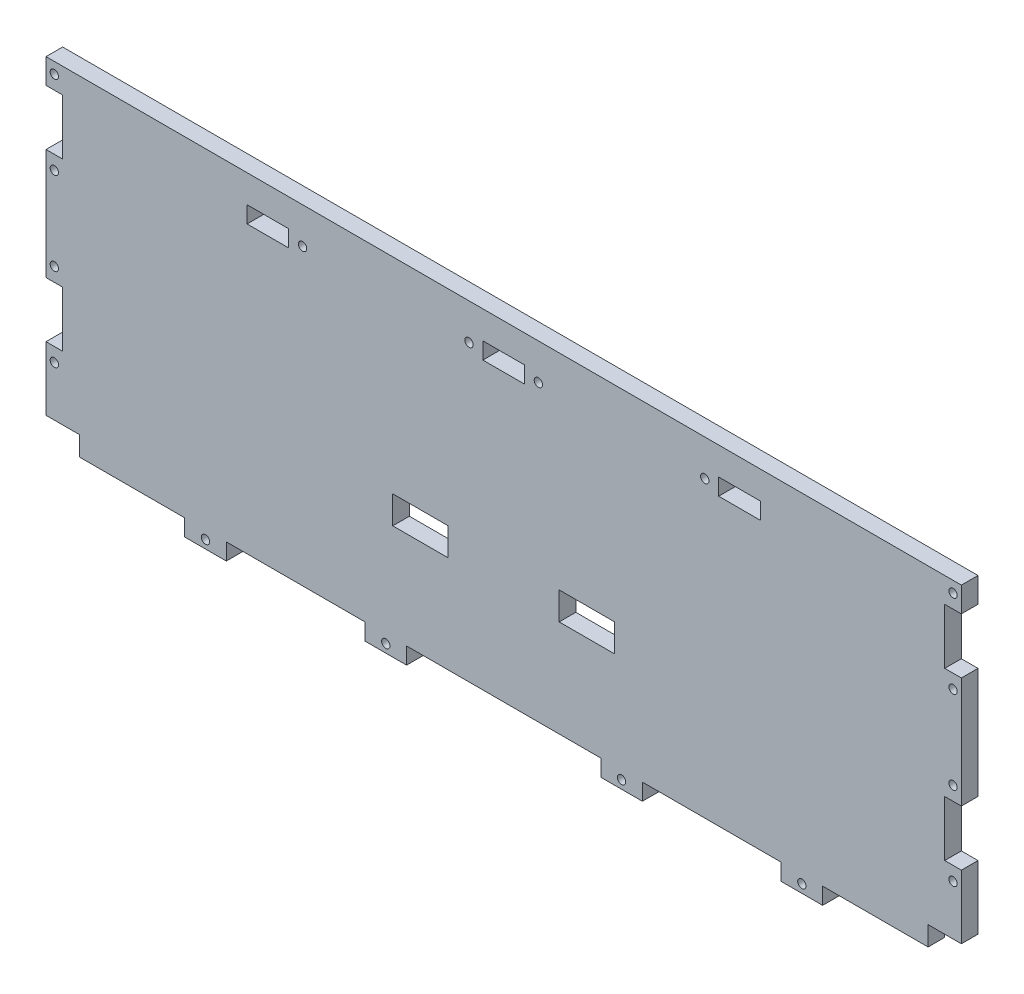
SolidWorks part; units mm, degrees
ref_plane "Plan de face" through (0, 0, 0) normal (0, 0, 1) x (1, 0, 0)
ref_plane "Plan de dessus" through (0, 0, 0) normal (0, 1, 0) x (1, 0, 0)
ref_plane "Plan de droite" through (0, 0, 0) normal (1, 0, 0) x (0, 0, -1)
sketch "Esquisse1" plane through (0, 0, 0) normal (0, 0, 1) x (1, 0, 0)
  line L0 (97.3951, 0) -> (-118.5049, 0) construction
  line L1 (-165, 119) -> (165, 119)
  line L2 (-165, 119) -> (-165, -119)
  line L3 (-165, -119) -> (165, -119)
  line L4 (165, 119) -> (165, -119)
  line L5 (0, 79.3588) -> (0, -79.3588) construction
  line L6 (-92.5, -10) -> (-77.5, -10)
  line L7 (-92.5, -10) -> (-92.5, -16)
  line L8 (-92.5, -16) -> (-77.5, -16)
  line L9 (-77.5, -10) -> (-77.5, -16)
  line L10 (-7.5, -10) -> (7.5, -10)
  line L11 (-7.5, -10) -> (-7.5, -16)
  line L12 (-7.5, -16) -> (7.5, -16)
  line L13 (7.5, -10) -> (7.5, -16)
  line L14 (77.5, -10) -> (92.5, -10)
  line L15 (77.5, -10) -> (77.5, -16)
  line L16 (77.5, -16) -> (92.5, -16)
  line L17 (92.5, -10) -> (92.5, -16)
  line L18 (20, -74) -> (20, -84)
  line L19 (-40, -74) -> (-20, -74)
  line L20 (-40, -74) -> (-40, -84)
  line L21 (-40, -84) -> (-20, -84)
  line L22 (-20, -74) -> (-20, -84)
  line L23 (40, -84) -> (20, -84)
  line L24 (40, -74) -> (40, -84)
  line L25 (40, -74) -> (20, -74)
  dimension "D1" = 238
  dimension "D2" = 330
  dimension "D3" = 165
  dimension "D4" = 119
  dimension "D5" = 15
  dimension "D6" = 6
  dimension "D7" = 6
  dimension "D8" = 15
  dimension "D9" = 6
  dimension "D10" = 15
  dimension "D11" = 70
  dimension "D12" = 70
  dimension "D13" = 103
  dimension "D14" = 72.5
  dimension "D15" = 10
  dimension "D16" = 20
  dimension "D17" = 35
  dimension "D18" = 40
extrude "Boss.-Extru.1" add sketch "Esquisse1" along normal blind 6
sketch "Esquisse2" plane through (0, 0, 6) normal (0, 0, 1) x (1, 0, 0)
  line L0 (243.146, 0) -> (-260.0003, 0) construction
  line L1 (0, 180.4713) -> (0, -129.6072) construction
  line L3 (-165, -119) -> (165, -119) construction
  line L4 (-115, -119) -> (-100, -119)
  line L5 (-115, -119) -> (-115, -125)
  line L6 (-115, -125) -> (-100, -125)
  line L8 (-100, -119) -> (-100, -125)
  line L9 (-165, 119) -> (-165, -119) construction
  line L10 (-50, -119) -> (-35, -119)
  line L11 (-50, -119) -> (-50, -125)
  line L12 (-50, -125) -> (-35, -125)
  line L13 (-35, -119) -> (-35, -125)
  line L14 (35, -119) -> (35, -125)
  line L15 (50, -125) -> (35, -125)
  line L16 (50, -119) -> (50, -125)
  line L17 (50, -119) -> (35, -119)
  line L18 (100, -119) -> (100, -125)
  line L19 (115, -125) -> (100, -125)
  line L20 (115, -119) -> (115, -125)
  line L21 (115, -119) -> (100, -119)
  line M9 (-165, -119) -> (165, -119)
  line M11 (165, 119) -> (-165, 119)
  dimension "D1" = 15
  dimension "D2" = 15
  dimension "D3" = 6
  dimension "D4" = 6
  dimension "D5" = 50
  dimension "D6" = 50
extrude "Boss.-Extru.2" add sketch "Esquisse2" against normal blind 6 contours M11 | M11 | M11 | M11 | M9 | M9 | M9 | M9 region at (107.5, -122, 6) region at (42.5, -122, 6) region at (-42.5, -122, 6) region at (-107.5, -122, 6)
sketch "Esquisse3" plane through (0, 0, 6) normal (0, 0, 1) x (1, 0, 0)
  line L0 (-165, 119) -> (-165, -119) construction
  line L1 (-165, 69) -> (-159, 69)
  line L2 (-165, 69) -> (-165, 89)
  line L3 (-165, 89) -> (-159, 89)
  line L4 (-159, 69) -> (-159, 89)
  line L5 (234.1368, 0) -> (-337.9213, 0) construction
  line L6 (-165, 29) -> (-159, 29)
  line L7 (-165, 29) -> (-165, 9)
  line L8 (-165, 9) -> (-159, 9)
  line L9 (-159, 29) -> (-159, 9)
  line L10 (0, 279.7488) -> (0, -188.1201) construction
  line L11 (165, 119) -> (-165, 119) construction
  line L12 (-159, -29) -> (-159, -9)
  line L13 (-165, -9) -> (-159, -9)
  line L14 (-165, -29) -> (-165, -9)
  line L15 (-165, -29) -> (-159, -29)
  line L16 (-159, -69) -> (-159, -89)
  line L17 (-165, -89) -> (-159, -89)
  line L18 (-165, -69) -> (-165, -89)
  line L19 (-165, -69) -> (-159, -69)
  line L20 (165, -69) -> (159, -69)
  line L21 (165, -69) -> (165, -89)
  line L22 (165, -89) -> (159, -89)
  line L23 (159, -69) -> (159, -89)
  line L24 (165, -29) -> (159, -29)
  line L25 (165, -29) -> (165, -9)
  line L26 (165, -9) -> (159, -9)
  line L27 (159, -29) -> (159, -9)
  line L28 (159, 29) -> (159, 9)
  line L29 (165, 9) -> (159, 9)
  line L30 (165, 29) -> (165, 9)
  line L31 (165, 29) -> (159, 29)
  line L32 (159, 69) -> (159, 89)
  line L33 (165, 89) -> (159, 89)
  line L34 (165, 69) -> (165, 89)
  line L35 (165, 69) -> (159, 69)
  line L36 (153, -119) -> (153, -112)
  line L37 (-165, -119) -> (-153, -119)
  line L38 (-165, -119) -> (-165, -112)
  line L39 (-165, -112) -> (-153, -112)
  line L40 (-153, -119) -> (-153, -112)
  line L41 (165, -112) -> (153, -112)
  line L42 (165, -119) -> (165, -112)
  line L43 (165, -119) -> (153, -119)
  dimension "D1" = 40
  dimension "D2" = 6
  dimension "D3" = 6
  dimension "D4" = 20
  dimension "D5" = 20
  dimension "D6" = 30
  dimension "D7" = 12
  dimension "D8" = 7
extrude "Enlèv. mat.-Extru.1" cut sketch "Esquisse3" against normal blind 6
sketch "Esquisse4" plane through (0, 0, 6) normal (0, 0, 1) x (1, 0, 0)
  line L0 (-162, 121.7279) -> (-162, -131.0602) construction
  line L1 (0, 158.5579) -> (0, -182.4489) construction
  line L2 (165, 119) -> (-165, 119) construction
  line L3 (-106.4439, -13) -> (117.3944, -13) construction
  line L4 (-159, 89) -> (-165, 89) construction
  line L5 (-165, 119) -> (-165, 89) construction
  line L6 (-165, 69) -> (-159, 69) construction
  line L7 (-159, 29) -> (-165, 29) construction
  line L8 (-165, 9) -> (-159, 9) construction
  line L9 (-159, -9) -> (-165, -9) construction
  line L10 (-115, -125) -> (-100, -125) construction
  line L11 (-77.5, -16) -> (-77.5, -10) construction
  line L12 (-165, -29) -> (-159, -29) construction
  line L13 (-159, -69) -> (-165, -69) construction
  line L14 (-165, -89) -> (-159, -89) construction
  line L15 (-7.5, -10) -> (-7.5, -16) construction
  line L16 (162, 121.7279) -> (162, -131.0602) construction
  line L17 (-127.292, -122) -> (137.4892, -122) construction
  line L18 (-77.5, -10) -> (-92.5, -10) construction
  line L21 (-115, -119) -> (-115, -125) construction
  line L22 (-50, -119) -> (-50, -125) construction
  circle A0 centre (-162, 114) radius 1.5
  circle A1 centre (-162, 94) radius 1.5
  circle A2 centre (-162, 64) radius 1.5
  circle A3 centre (-162, 34) radius 1.5
  circle A4 centre (-162, 4) radius 1.5
  circle A5 centre (-107.5, -122) radius 1.5
  circle A6 centre (-162, -4) radius 1.5
  circle A7 centre (-162, -34) radius 1.5
  circle A8 centre (-162, -64) radius 1.5
  circle A9 centre (-162, -94) radius 1.5
  circle A10 centre (-42.5, -122) radius 1.5
  circle A11 centre (-72.5, -13) radius 1.5
  circle A12 centre (162, -94) radius 1.5
  circle A13 centre (162, -64) radius 1.5
  circle A14 centre (162, -34) radius 1.5
  circle A15 centre (162, -4) radius 1.5
  circle A16 centre (42.5, -122) radius 1.5
  circle A17 centre (162, 4) radius 1.5
  circle A18 centre (162, 34) radius 1.5
  circle A19 centre (162, 64) radius 1.5
  circle A20 centre (162, 94) radius 1.5
  circle A21 centre (162, 114) radius 1.5
  circle A22 centre (-12.5, -13) radius 1.5
  circle A23 centre (12.5, -13) radius 1.5
  circle A24 centre (72.5, -13) radius 1.5
  circle A25 centre (107.5, -122) radius 1.5
  dimension "D1" = 3
  dimension "D2" = 3
  dimension "D3" = 3
  dimension "D4" = 3
  dimension "D5" = 3
  dimension "D6" = 3
  dimension "D7" = 3
  dimension "D8" = 3
  dimension "D9" = 3
  dimension "D10" = 3
  dimension "D11" = 3
  dimension "D12" = 5
  dimension "D13" = 5
  dimension "D15" = 5
  dimension "D16" = 5
  dimension "D17" = 5
  dimension "D19" = 3
  dimension "D20" = 5
  dimension "D21" = 5
  dimension "D23" = 3
  dimension "D24" = 3
  dimension "D25" = 7.5
  dimension "D26" = 5
  dimension "D27" = 5
  dimension "D28" = 7.5
  dimension "D14" = 3
  dimension "D18" = 5
  dimension "D22" = 5
  dimension "D29" = 3
extrude "Enlèv. mat.-Extru.2" cut sketch "Esquisse4" against normal blind 6
sketch "Esquisse5" plane through (0, 0, 6) normal (0, 0, 1) x (1, 0, 0)
  line L1 (-174.9982, 0) -> (181.1877, 0)
  line L2 (-174.9982, 0) -> (-174.9982, 137.1433)
  line L3 (-174.9982, 137.1433) -> (181.1877, 137.1433)
  line L4 (181.1877, 0) -> (181.1877, 137.1433)
extrude "Enlèv. mat.-Extru.3" cut sketch "Esquisse5" against normal blind 6
sketch "Esquisse6" plane through (0, 0, 6) normal (0, 0, 1) x (1, 0, 0)
  line L0 (-103.8163, -14.4996) -> (134.12, -14.4996) construction
  arc A0 (-103.2691, -14.4996) -> (-23.2691, -14.4996) centre (-63.2691, -14.4996) cw construction
  arc A1 (31.4727, -14.4996) -> (113.4572, -14.4996) centre (72.4649, -14.4996) cw construction
  circle A2 centre (72.5, -13) radius 1.5 construction
  text T0 "<b> ESME SUDRIA</b>" font "BankGothic Lt BT" height in points 36
  text T2 "<b> ELSYS DESIGN</b>" font "BankGothic Lt BT" height in points 36
  dimension "D1" = 40
equation "\"D3@Esquisse1\"=\"D2@Esquisse1\"/2"
equation "\"D4@Esquisse1\"=\"D1@Esquisse1\"/2"
